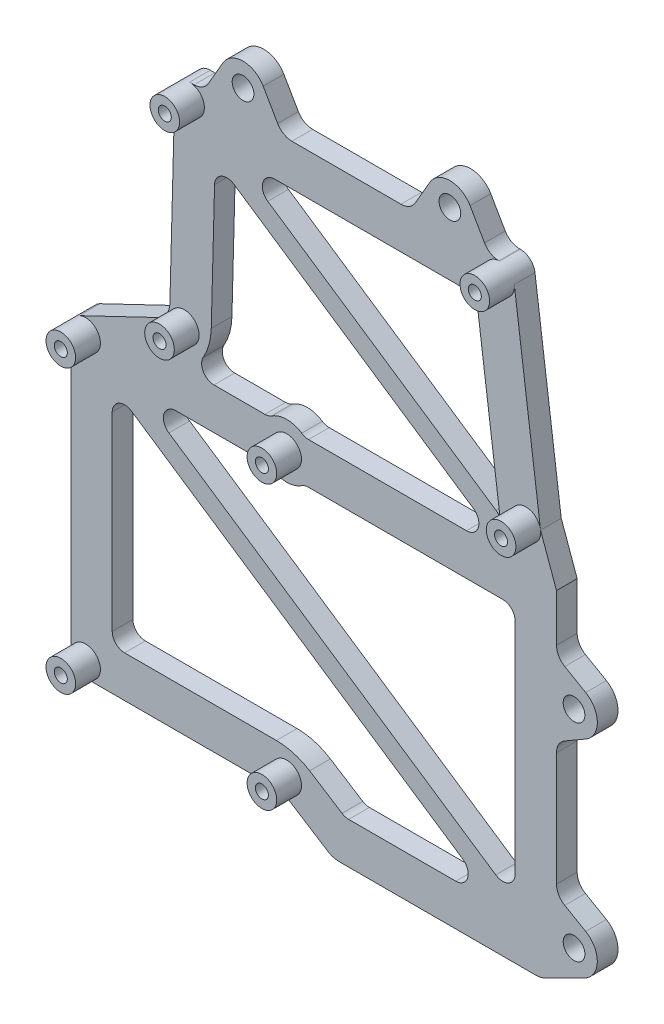
SolidWorks part; units mm, degrees
ref_plane "Front Plane" through (0, 0, 0) normal (0, 0, 1) x (1, 0, 0)
ref_plane "Top Plane" through (0, 0, 0) normal (0, 1, 0) x (1, 0, 0)
ref_plane "Right Plane" through (0, 0, 0) normal (1, 0, 0) x (0, 0, -1)
sketch "Sketch1" plane through (0, 0, 0) normal (0, 0, 1) x (1, 0, 0)
  line L0 (-89.9435, -52.835) -> (-7.3935, -52.835) construction
  line L1 (-88.6735, -4.575) -> (-13.7435, -4.575) construction
  line L2 (-89.9435, -52.835) -> (-13.7435, -4.575) construction
  line L3 (-88.6735, -4.575) -> (-7.3935, -52.835) construction
  line L4 (-88.6735, -3) -> (-13.7435, -3) construction
  line L5 (0, 0) -> (-100, 0) construction
  line L6 (0, 0) -> (0, -55.0748) construction
  line L7 (0, -55.0748) -> (-100, -55.0748) construction
  line L8 (-100, 0) -> (-100, -55.0748) construction
  line L9 (0, 0) -> (-100, -55.0748) construction
  line L10 (0, -55.0748) -> (-100, 0) construction
  line L11 (-113.8, -66.4248) -> (-65.2, -66.4248) construction
  line L12 (-62, -138.0748) -> (-117, -138.0748) construction
  line L13 (-62, -138.0748) -> (-62, -63.0748) construction
  line L14 (-62, -63.0748) -> (-117, -63.0748) construction
  line L15 (-117, -138.0748) -> (-117, -63.0748) construction
  line L16 (-62, -138.0748) -> (-117, -63.0748) construction
  line L17 (-62, -63.0748) -> (-117, -138.0748) construction
  line L18 (-65.2, -66.4248) -> (-65.2, -134.7248) construction
  line L19 (-65.2, -134.7248) -> (-113.8, -134.7248) construction
  line L20 (-65.2, -100.5748) -> (-89.5, -100.5748) construction
  line L21 (-89.5, -100.5748) -> (-89.5, -66.4248) construction
  line L22 (-93.5173, -52.7409) -> (-92.2485, -4.575)
  line L23 (0, -146.0748) -> (-54, -146.0748)
  line L24 (0, -146.0748) -> (0, -63.0748)
  line L25 (0, -63.0748) -> (-54, -63.0748) construction
  line L26 (-54, -146.0748) -> (-54, -63.0748) construction
  line L27 (0, -146.0748) -> (-54, -63.0748) construction
  line L28 (0, -63.0748) -> (-54, -146.0748) construction
  line L29 (-88.6735, -1) -> (-13.7435, -1)
  line L30 (-10.1991, -4.1086) -> (-3.8491, -52.3686)
  line L31 (-3.8491, -52.3686) -> (0, -63.0748)
  line L32 (-54, -146.0748) -> (-66.2395, -138.2998)
  line L33 (-66.2395, -138.2998) -> (-113.8, -138.2998)
  line L34 (-117.375, -134.7248) -> (-117.375, -66.4248)
  line L35 (-115.3449, -63.2009) -> (-93.5173, -52.7409)
  circle A0 centre (-88.6735, -4.575) radius 1.575 construction
  circle A1 centre (-13.7435, -4.575) radius 1.575 construction
  circle A2 centre (-89.9435, -52.835) radius 1.575 construction
  circle A3 centre (-7.3935, -52.835) radius 1.575 construction
  circle A4 centre (-113.8, -66.4248) radius 1.575 construction
  circle A5 centre (-65.2, -66.4248) radius 1.575 construction
  circle A6 centre (-113.8, -134.7248) radius 1.575 construction
  circle A7 centre (-65.2, -134.7248) radius 1.575 construction
  circle A8 centre (-89.9435, -52.835) radius 3.575 construction
  circle A9 centre (-88.6735, -4.575) radius 3.575 construction
  circle A10 centre (-13.7435, -4.575) radius 3.575 construction
  circle A11 centre (-7.3935, -52.835) radius 3.575 construction
  circle A12 centre (-113.8, -66.4248) radius 3.575 construction
  circle A13 centre (-65.2, -66.4248) radius 3.575 construction
  circle A14 centre (-113.8, -134.7248) radius 3.575 construction
  circle A15 centre (-65.2, -134.7248) radius 3.575 construction
  arc A16 (-88.6735, -1) -> (-92.2485, -4.575) centre (-88.6735, -4.575) ccw
  arc A17 (-10.1991, -4.1086) -> (-13.7435, -1) centre (-13.7435, -4.575) ccw
  arc A18 (-117.375, -134.7248) -> (-113.8, -138.2998) centre (-113.8, -134.7248) ccw
  arc A19 (-117.375, -66.4248) -> (-115.3449, -63.2009) centre (-113.8, -66.4248) cw
  point P8 (-50, -27.5374)
  point P17 (-89.5, -100.5748)
  point P31 (-27, -104.5748)
  dimension "D1" = 3.15
  dimension "D10" = 68.3
  dimension "D17" = 2
  dimension "D18" = 3.575
  dimension "D19" = 3.575
  dimension "D20" = 3.575
  dimension "D21" = 3.575
  dimension "D2" = 74.93
  dimension "D3" = 48.26
  dimension "D4" = 1.27
  dimension "D5" = 82.55
  dimension "D6" = 3
  dimension "D7" = 100
  dimension "D8" = 75
  dimension "D9" = 55
  dimension "D11" = 48.6
  dimension "D12" = 8
  dimension "D13" = 83
  dimension "D14" = 54
  dimension "D15" = 8
  dimension "D16" = 8
extrude "Boss-Extrude1" add sketch "Sketch1" along normal blind 5
fillet "Fillet1" radius 5 4 edges at (0, -146.0748, 2.5) (-54, -146.0748, 2.5) (-66.2395, -138.2998, 2.5) (-93.5173, -52.7409, 2.5)
sketch "Sketch2" plane through (0, 0, 5) normal (0, 0, 1) x (1, 0, 0)
  circle A0 centre (-113.8, -66.4248) radius 1.575 construction
  circle A1 centre (-113.8, -66.4248) radius 1.575
  circle A2 centre (-7.3935, -52.835) radius 1.575 construction
  circle A3 centre (-13.7435, -4.575) radius 1.575 construction
  circle A4 centre (-13.7435, -4.575) radius 3.575 construction
  circle A5 centre (-7.3935, -52.835) radius 3.575 construction
  circle A6 centre (-89.9435, -52.835) radius 3.575 construction
  circle A7 centre (-89.9435, -52.835) radius 1.575 construction
  circle A8 centre (-88.6735, -4.575) radius 1.575 construction
  circle A9 centre (-88.6735, -4.575) radius 3.575 construction
  circle A10 centre (-65.2, -134.7248) radius 1.575 construction
  circle A11 centre (-65.2, -134.7248) radius 3.575 construction
  circle A12 centre (-65.2, -66.4248) radius 1.575 construction
  circle A13 centre (-65.2, -66.4248) radius 3.575 construction
  circle A14 centre (-113.8, -66.4248) radius 3.575 construction
  circle A15 centre (-113.8, -134.7248) radius 3.575 construction
  circle A16 centre (-113.8, -134.7248) radius 1.575 construction
  circle A17 centre (-7.3935, -52.835) radius 1.575
  circle A18 centre (-13.7435, -4.575) radius 1.575
  circle A19 centre (-13.7435, -4.575) radius 3.575
  circle A20 centre (-7.3935, -52.835) radius 3.575
  circle A21 centre (-89.9435, -52.835) radius 3.575
  circle A22 centre (-89.9435, -52.835) radius 1.575
  circle A23 centre (-88.6735, -4.575) radius 1.575
  circle A24 centre (-88.6735, -4.575) radius 3.575
  circle A25 centre (-65.2, -134.7248) radius 1.575
  circle A26 centre (-65.2, -134.7248) radius 3.575
  circle A27 centre (-65.2, -66.4248) radius 1.575
  circle A28 centre (-65.2, -66.4248) radius 3.575
  circle A29 centre (-113.8, -66.4248) radius 3.575
  circle A30 centre (-113.8, -134.7248) radius 3.575
  circle A31 centre (-113.8, -134.7248) radius 1.575
extrude "Boss-Extrude2" add sketch "Sketch2" along normal blind 6
sketch "Sketch3" plane through (0, 0, 5) normal (0, 0, 1) x (1, 0, 0)
  line L0 (-65.2, -61.4248) -> (-100.6345, -61.4248) construction
  line L1 (-65.2, -61.4248) -> (-10, -61.4248) construction
  line L2 (-91.9528, -63.0801) -> (-107.375, -70.4705) construction
  line L3 (-107.375, -70.4705) -> (-107.375, -128.2998) construction
  line L4 (-65.2, -66.4248) -> (-100.6345, -66.4248) construction
  line L5 (-10, -64.8178) -> (-13.6233, -54.7396) construction
  line L6 (-10, -136.0748) -> (-10, -64.8178) construction
  line L7 (-65.2, -66.4248) -> (-10, -66.4248) construction
  line L8 (0, -141.0748) -> (0, -63.0748) construction
  line L9 (-65.2, -71.4248) -> (-10, -71.4248) construction
  line L10 (-113.8, -66.4248) -> (-10, -136.0748) construction
  line L11 (-82.4143, -11) -> (0, -66.4248) construction
  line L12 (-107.375, -73.7467) -> (-14.4868, -136.0748)
  line L13 (-101.8617, -71.4248) -> (-10, -133.0642)
  line L14 (-82.4923, -13.9603) -> (-11.9146, -61.4248)
  line L15 (-77.9345, -11) -> (-13.8554, -54.0941)
  line L16 (-112.407, -64.3489) -> (-8.607, -133.9989) construction
  line L17 (-115.193, -68.5008) -> (-11.393, -138.1508) construction
  line L18 (-51.0923, -136.0748) -> (-10, -136.0748) construction
  line L19 (-81.0192, -8.9255) -> (1.3951, -64.3503) construction
  line L20 (-19.3785, -11) -> (-82.4143, -11) construction
  line L21 (-83.8095, -13.0745) -> (-1.3951, -68.4993) construction
  line L22 (-82.4143, -11) -> (-83.4403, -49.948) construction
  line L30 (-10, -133.0642) -> (-10, -71.4248)
  line L31 (-13.8554, -54.0941) -> (-13.6233, -54.7396)
  line L32 (-13.6233, -54.7396) -> (-19.3785, -11)
  line L33 (-19.3785, -11) -> (-77.9345, -11)
  line L34 (-82.4923, -13.9603) -> (-83.4403, -49.948)
  line L36 (-107.375, -73.7467) -> (-107.375, -128.2998)
  line L37 (-107.375, -128.2998) -> (-67.6933, -128.2998)
  line L38 (-59.6503, -130.6385) -> (-51.0923, -136.0748)
  line L39 (-51.0923, -136.0748) -> (-14.4868, -136.0748)
  line L40 (0, -141.0748) -> (0, -63.0748)
  line L41 (-52.5462, -146.0748) -> (-5, -146.0748)
  line L42 (-65.0123, -139.0794) -> (-55.2272, -145.2953)
  line L43 (-113.8, -138.2998) -> (-67.6933, -138.2998)
  line L44 (-117.375, -66.4248) -> (-117.375, -134.7248)
  line L45 (-96.2743, -54.062) -> (-115.3449, -63.2009)
  line L46 (-92.2485, -4.575) -> (-93.4368, -49.6847)
  line L47 (-13.7435, -1) -> (-88.6735, -1)
  line L48 (-3.8491, -52.3686) -> (-10.1991, -4.1086)
  line L49 (0, -63.0748) -> (-3.8491, -52.3686)
  line L50 (0, -141.0748) -> (0, -63.0748)
  line L51 (-52.5462, -146.0748) -> (-5, -146.0748)
  line L52 (-65.0123, -139.0794) -> (-55.2272, -145.2953)
  line L53 (-113.8, -138.2998) -> (-67.6933, -138.2998)
  line L54 (-117.375, -66.4248) -> (-117.375, -134.7248)
  line L55 (-96.2743, -54.062) -> (-115.3449, -63.2009)
  line L56 (-92.2485, -4.575) -> (-93.4368, -49.6847)
  line L57 (-13.7435, -1) -> (-88.6735, -1)
  line L58 (-3.8491, -52.3686) -> (-10.1991, -4.1086)
  line L59 (0, -63.0748) -> (-3.8491, -52.3686)
  line L60 (-65.2, -66.4248) -> (0, -66.4248) construction
  line L61 (-65.2, -66.4248) -> (-110.225, -66.4248) construction
  line L62 (-69.4697, -71.4248) -> (-101.8617, -71.4248)
  line L63 (-60.9303, -71.4248) -> (-10, -71.4248)
  line L64 (-69.4697, -61.4248) -> (-89.2666, -61.4248)
  line L65 (-60.9303, -61.4248) -> (-11.9146, -61.4248)
  line L66 (-65.2, -71.4248) -> (-100.6345, -71.4248) construction
  arc A0 (-91.9528, -63.0801) -> (-83.4403, -49.948) centre (-98.4351, -49.553) ccw construction
  circle A1 centre (-113.8, -66.4248) radius 3.575 construction
  arc A2 (-117.375, -66.4248) -> (-115.3449, -63.2009) centre (-113.8, -66.4248) ccw construction
  arc A3 (-69.4697, -71.4248) -> (-60.9303, -71.4248) centre (-65.2, -66.4248) ccw
  arc A27 (-19.3785, -11) -> (-19.3785, -11) centre (-19.3785, -11) ccw
  arc A28 (-82.4143, -11) -> (-82.4143, -11) centre (-82.4143, -11) ccw
  arc A29 (-89.2666, -61.4248) -> (-83.4403, -49.948) centre (-98.4351, -49.553) ccw
  arc A30 (-107.375, -70.4705) -> (-107.375, -70.4705) centre (-107.375, -70.4705) ccw
  arc A31 (-107.375, -128.2998) -> (-107.375, -128.2998) centre (-107.375, -128.2998) ccw
  arc A32 (-59.6503, -130.6385) -> (-67.6933, -128.2998) centre (-67.6933, -143.2998) ccw
  arc A33 (-51.0923, -136.0748) -> (-51.0923, -136.0748) centre (-51.0923, -136.0748) ccw
  arc A34 (-10, -136.0748) -> (-10, -136.0748) centre (-10, -136.0748) ccw
  arc A35 (-5, -146.0748) -> (0, -141.0748) centre (-5, -141.0748) ccw
  arc A36 (-55.2272, -145.2953) -> (-52.5462, -146.0748) centre (-52.5462, -141.0748) ccw
  arc A37 (-65.0123, -139.0794) -> (-67.6933, -138.2998) centre (-67.6933, -143.2998) ccw
  arc A38 (-117.375, -134.7248) -> (-113.8, -138.2998) centre (-113.8, -134.7248) ccw
  arc A39 (-115.3449, -63.2009) -> (-117.375, -66.4248) centre (-113.8, -66.4248) ccw
  arc A40 (-96.2743, -54.062) -> (-93.4368, -49.6847) centre (-98.4351, -49.553) ccw
  arc A41 (-88.6735, -1) -> (-92.2485, -4.575) centre (-88.6735, -4.575) ccw
  arc A42 (-10.1991, -4.1086) -> (-13.7435, -1) centre (-13.7435, -4.575) ccw
  arc A43 (-5, -146.0748) -> (0, -141.0748) centre (-5, -141.0748) ccw
  arc A44 (-55.2272, -145.2953) -> (-52.5462, -146.0748) centre (-52.5462, -141.0748) ccw
  arc A45 (-65.0123, -139.0794) -> (-67.6933, -138.2998) centre (-67.6933, -143.2998) ccw
  arc A46 (-117.375, -134.7248) -> (-113.8, -138.2998) centre (-113.8, -134.7248) ccw
  arc A47 (-115.3449, -63.2009) -> (-117.375, -66.4248) centre (-113.8, -66.4248) ccw
  arc A48 (-96.2743, -54.062) -> (-93.4368, -49.6847) centre (-98.4351, -49.553) ccw
  arc A49 (-88.6735, -1) -> (-92.2485, -4.575) centre (-88.6735, -4.575) ccw
  arc A50 (-10.1991, -4.1086) -> (-13.7435, -1) centre (-13.7435, -4.575) ccw
  arc A51 (-60.9303, -61.4248) -> (-69.4697, -61.4248) centre (-65.2, -66.4248) ccw
  circle A52 centre (-65.2, -66.4248) radius 3.575 construction
  circle A53 centre (-65.2, -66.4248) radius 3.575
  dimension "D3" = 3
  dimension "D1" = 0
  dimension "D2" = 10
  dimension "D4" = 5
  dimension "D5" = 5
  dimension "D6" = 2.5
  dimension "D7" = 2.5
  dimension "D8" = 2.5
  dimension "D9" = 2.5
extrude "Cut-Extrude1" cut sketch "Sketch3" against normal up to surface (5 mm away) contours A51 L65 L14 L34 A29 L64 | L32 L33 L15 L31 | A3 L62 L13 L30 L63 | A32 L38 L39 L12 L36 L37 region at (-75.5074, -112.6557, 5) region at (-40.5404, -92.0362, 5) region at (-59.6405, -45.6677, 5) region at (-37.0016, -25.4018, 5) up to face at (-61.5282, -82.7166, 0)
sketch "Sketch4" plane through (0, 0, 0) normal (0, 0, 1) x (1, 0, 0)
  line L0 (-126.2586, 4.2426) -> (4.2426, 4.2426) construction
  line L1 (4.2426, 4.2426) -> (4.2426, -135.7574) construction
  line L2 (0, 0) -> (4.2426, 4.2426) construction
  line L3 (-75.7574, 4.2426) -> (-75.7574, -1) construction
  line L4 (-80.6288, 7.0551) -> (-85.2794, -1)
  line L5 (-70.886, 7.0551) -> (-66.2353, -1)
  line L6 (-85.2794, -1) -> (-66.2353, -1)
  line L7 (-25.7574, 4.2426) -> (-25.7574, -1) construction
  line L8 (-30.6288, 7.0551) -> (-35.2794, -1)
  line L9 (-20.886, 7.0551) -> (-16.2353, -1)
  line L10 (-35.2794, -1) -> (-16.2353, -1)
  line L11 (4.2426, -85.7574) -> (0, -85.7574) construction
  line L12 (7.0551, -80.886) -> (0, -76.8127)
  line L13 (0, -141.0748) -> (0, -63.0748)
  line L14 (-52.5462, -146.0748) -> (-5, -146.0748)
  line L15 (-65.0123, -139.0794) -> (-55.2272, -145.2953)
  line L16 (-113.8, -138.2998) -> (-67.6933, -138.2998)
  line L17 (-117.375, -66.4248) -> (-117.375, -134.7248)
  line L18 (-96.2743, -54.062) -> (-115.3449, -63.2009)
  line L19 (-92.2485, -4.575) -> (-93.4368, -49.6847)
  line L20 (-13.7435, -1) -> (-88.6735, -1)
  line L21 (-3.8491, -52.3686) -> (-10.1991, -4.1086)
  line L22 (0, -63.0748) -> (-3.8491, -52.3686)
  line L23 (0, -141.0748) -> (0, -126.8127)
  line L25 (-65.0123, -139.0794) -> (-55.2272, -145.2953) construction
  line L26 (-113.8, -138.2998) -> (-67.6933, -138.2998) construction
  line L27 (-117.375, -66.4248) -> (-117.375, -134.7248) construction
  line L28 (-96.2743, -54.062) -> (-115.3449, -63.2009) construction
  line L29 (-92.2485, -4.575) -> (-93.4368, -49.6847) construction
  line L30 (-13.7435, -1) -> (-88.6735, -1) construction
  line L31 (-3.8491, -52.3686) -> (-10.1991, -4.1086) construction
  line L32 (0, -63.0748) -> (-3.8491, -52.3686) construction
  line L33 (0, -76.8127) -> (0, -94.702)
  line L34 (0, -94.702) -> (7.0551, -90.6288)
  line L35 (0, -126.8127) -> (7.0551, -130.886)
  line L36 (-2.7649, -145.5475) -> (6.7571, -140.7891)
  line L37 (4.2426, -135.7574) -> (0, -135.7574) construction
  line L38 (0, -94.702) -> (0, -63.0748) construction
  circle A0 centre (-75.7574, 4.2426) radius 2.625
  circle A1 centre (-25.7574, 4.2426) radius 2.625
  circle A2 centre (4.2426, -85.7574) radius 2.625
  circle A3 centre (4.2426, -135.7574) radius 2.625
  circle A4 centre (-75.7574, 4.2426) radius 5.625 construction
  circle A5 centre (-25.7574, 4.2426) radius 5.625 construction
  circle A6 centre (4.2426, -85.7574) radius 5.625 construction
  circle A7 centre (4.2426, -135.7574) radius 5.625 construction
  arc A8 (-80.6288, 7.0551) -> (-70.886, 7.0551) centre (-75.7574, 4.2426) cw
  arc A9 (-30.6288, 7.0551) -> (-20.886, 7.0551) centre (-25.7574, 4.2426) cw
  arc A10 (7.0551, -80.886) -> (7.0551, -90.6288) centre (4.2426, -85.7574) cw
  arc A11 (7.0551, -130.886) -> (6.7571, -140.7891) centre (4.2426, -135.7574) cw
  arc A16 (-5, -146.0748) -> (0, -141.0748) centre (-5, -141.0748) ccw
  arc A17 (-55.2272, -145.2953) -> (-52.5462, -146.0748) centre (-52.5462, -141.0748) ccw
  arc A18 (-65.0123, -139.0794) -> (-67.6933, -138.2998) centre (-67.6933, -143.2998) ccw
  arc A19 (-117.375, -134.7248) -> (-113.8, -138.2998) centre (-113.8, -134.7248) ccw
  arc A20 (-115.3449, -63.2009) -> (-117.375, -66.4248) centre (-113.8, -66.4248) ccw
  arc A21 (-96.2743, -54.062) -> (-93.4368, -49.6847) centre (-98.4351, -49.553) ccw
  arc A22 (-88.6735, -1) -> (-92.2485, -4.575) centre (-88.6735, -4.575) ccw
  arc A23 (-10.1991, -4.1086) -> (-13.7435, -1) centre (-13.7435, -4.575) ccw
  arc A24 (-2.7649, -145.5475) -> (0, -141.0748) centre (-5, -141.0748) ccw
  arc A25 (-55.2272, -145.2953) -> (-52.5462, -146.0748) centre (-52.5462, -141.0748) ccw construction
  arc A26 (-65.0123, -139.0794) -> (-67.6933, -138.2998) centre (-67.6933, -143.2998) ccw construction
  arc A27 (-117.375, -134.7248) -> (-113.8, -138.2998) centre (-113.8, -134.7248) ccw construction
  arc A28 (-115.3449, -63.2009) -> (-117.375, -66.4248) centre (-113.8, -66.4248) ccw construction
  arc A29 (-96.2743, -54.062) -> (-93.4368, -49.6847) centre (-98.4351, -49.553) ccw construction
  arc A30 (-88.6735, -1) -> (-92.2485, -4.575) centre (-88.6735, -4.575) ccw construction
  arc A31 (-10.1991, -4.1086) -> (-13.7435, -1) centre (-13.7435, -4.575) ccw construction
  dimension "D3" = 5.25
  dimension "D6" = 3
  dimension "D10" = 5.625
  dimension "D12" = 5.625
  dimension "D15" = 5.625
  dimension "D16" = 5.625
  dimension "D1" = 45
  dimension "D2" = 6
  dimension "D4" = 50
  dimension "D5" = 50
  dimension "D7" = 30
  dimension "D8" = 90
  dimension "D11" = 30
  dimension "D13" = 30
  dimension "D14" = 30
  dimension "D17" = 30
  dimension "D9" = 0
extrude "Boss-Extrude3" add sketch "Sketch4" along normal blind 5
fillet "Fillet2" [suppressed] radius 2
fillet "Fillet3" radius 3 17 edges at (-69.4697, -71.4248, 2.5) (-69.4697, -61.4248, 2.5) (-60.9303, -61.4248, 2.5) (-60.9303, -71.4248, 2.5) (-10, -71.4248, 2.5) (-10, -133.0642, 2.5) (-14.4868, -136.0748, 2.5) (-51.0923, -136.0748, 2.5) (-107.375, -128.2998, 2.5) (-107.375, -73.7467, 2.5) (-101.8617, -71.4248, 2.5) (-19.3785, -11, 2.5) (-13.8554, -54.0941, 2.5) (-11.9146, -61.4248, 2.5) (-89.2666, -61.4248, 2.5) (-77.9345, -11, 2.5) (-82.4923, -13.9603, 2.5)
fillet "Fillet4" radius 4 7 edges at (0, -126.8127, 2.5) (0, -94.702, 2.5) (0, -76.8127, 2.5) (-16.2353, -1, 2.5) (-35.2794, -1, 2.5) (-66.2353, -1, 2.5) (-85.2794, -1, 2.5)
